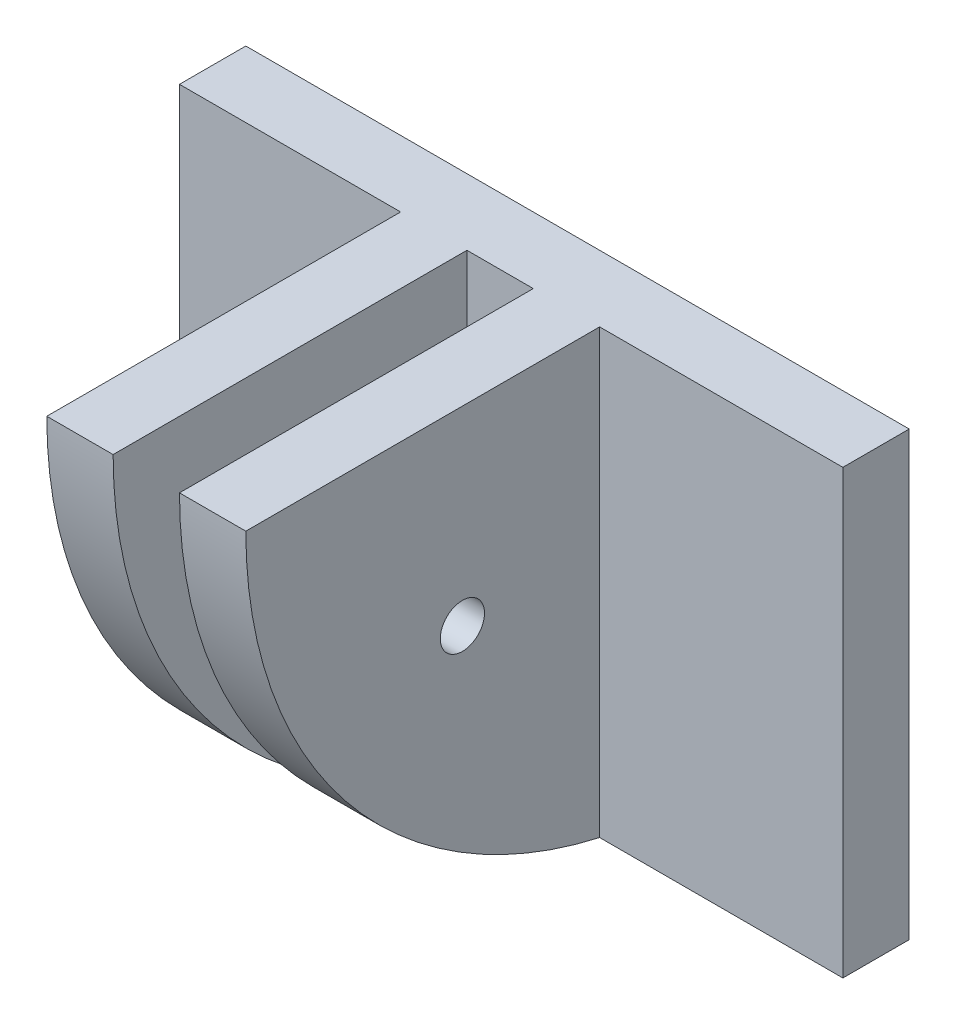
SolidWorks part; units mm, degrees
ref_plane "Ön Düzlem" through (0, 0, 0) normal (0, 0, 1) x (1, 0, 0)
ref_plane "Üst Düzlem" through (0, 0, 0) normal (0, 1, 0) x (1, 0, 0)
ref_plane "Sağ Düzlem" through (0, 0, 0) normal (1, 0, 0) x (0, 0, -1)
sketch "Çizim1" plane through (0, 0, 0) normal (0, 0, 1) x (1, 0, 0)
  line L1 (0, 0) -> (30, 0)
  line L2 (0, 0) -> (0, 20)
  line L3 (0, 20) -> (30, 20)
  line L4 (30, 0) -> (30, 20)
  dimension "D1" = 30
  dimension "D2" = 20
extrude "Yükseklik-Ekstrüzyon1" add sketch "Çizim1" along normal blind 3
sketch "Çizim2" plane through (0, 0, 0) normal (-1, 0, 0) x (0, 0, 1)
  line L0 (3, 0) -> (3, 20)
  line L1 (3, 20) -> (19, 20)
  arc A0 (19, 20) -> (3, 0) centre (-1.5, 20) cw
  dimension "D1" = 16
extrude "Yükseklik-Ekstrüzyon2" add sketch "Çizim2" against normal blind 3 from offset 10 offset against normal yes
extrude "Yükseklik-Ekstrüzyon3" add sketch "Çizim2<2>" against normal blind 3 from offset 16 offset against normal yes
sketch "Çizim2<2>" plane through (0, 0, 0) normal (-1, 0, 0) x (0, 0, 1) same geometry as "Çizim2"
sketch "Çizim3" plane through (10, 0, 0) normal (-1, 0, 0) x (0, 0, 1)
  circle A0 centre (9.2055, 11.3921) radius 1
  dimension "D1" = 2
extrude "Kes-Ekstrüzyon1" cut sketch "Çizim3" against normal blind 25
